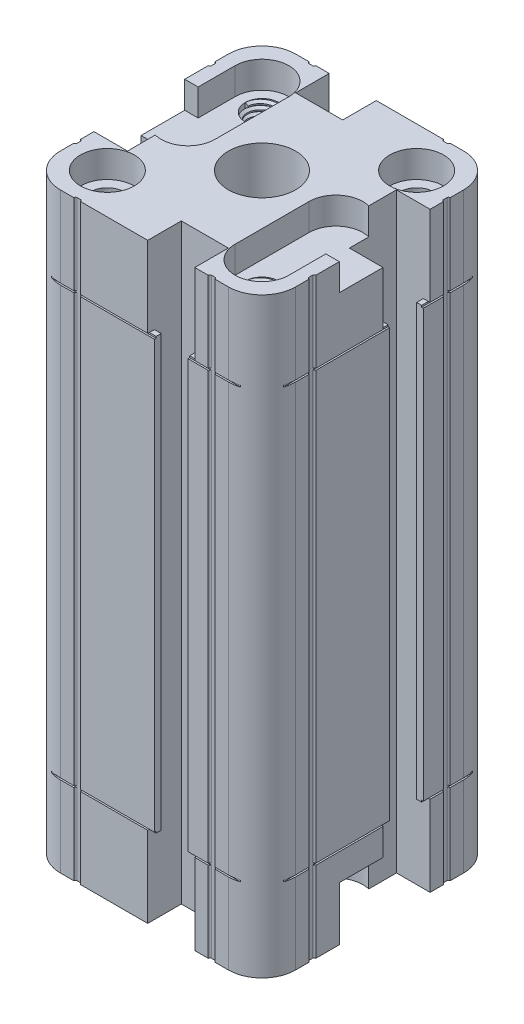
SolidWorks part; units mm, degrees
ref_plane "Front Plane" through (0, 0, 0) normal (0, 0, 1) x (1, 0, 0)
ref_plane "Top Plane" through (0, 0, 0) normal (0, 1, 0) x (1, 0, 0)
ref_plane "Right Plane" through (0, 0, 0) normal (1, 0, 0) x (0, 0, -1)
sketch "Sketch1" plane through (0, 0, 0) normal (0, 1, 0) x (1, 0, 0)
  line L1 (0, 0) -> (35, 0)
  line L2 (0, 0) -> (0, 35)
  line L3 (0, 35) -> (35, 35)
  line L4 (35, 0) -> (35, 35)
  dimension "D1" = 35
  dimension "D2" = 35
extrude "Boss-Extrude1" add sketch "Sketch1" along normal blind 88
sketch "Sketch2" plane through (0, 0, 0) normal (0, -1, 0) x (-1, 0, 0)
  line L0 (0, 0) -> (-35, 0) construction
  line L1 (0, 35) -> (0, 0) construction
  line L2 (-29, 6) -> (-29, 17) construction
  line L3 (-33, 6) -> (-33, 17)
  line L4 (-25, 6) -> (-25, 17)
  line L5 (-35, 0) -> (-35, 35) construction
  line L6 (-35, 35) -> (0, 35) construction
  line L7 (-6, 18) -> (-6, 29) construction
  line L8 (-10, 18) -> (-10, 29)
  line L9 (-2, 18) -> (-2, 29)
  circle A0 centre (-6, 6) radius 4
  circle A1 centre (-29, 29) radius 4
  arc A2 (-33, 6) -> (-25, 6) centre (-29, 6) ccw
  arc A3 (-25, 17) -> (-33, 17) centre (-29, 17) ccw
  arc A4 (-10, 18) -> (-2, 18) centre (-6, 18) ccw
  arc A5 (-2, 29) -> (-10, 29) centre (-6, 29) ccw
  point P10 (-29, 11.5)
  point P21 (-6, 23.5)
  dimension "D1" = 8
  dimension "D4" = 4
  dimension "D5" = 11
  dimension "D10" = 4
  dimension "D11" = 6
  dimension "D2" = 6
  dimension "D3" = 6
  dimension "D6" = 6
  dimension "D7" = 6
  dimension "D8" = 6
  dimension "D9" = 11
extrude "Cut-Extrude1" cut sketch "Sketch2" against normal blind 8
sketch "Sketch3" plane through (0, 0, 0) normal (0, -1, 0) x (-1, 0, 0)
  line L0 (0, 35) -> (0, 0) construction
  line L1 (-5, 23.5) -> (0, 23.5)
  line L2 (-5, 23.5) -> (-5, 14.127)
  line L3 (-5, 14.127) -> (0, 14.127)
  line L4 (0, 23.5) -> (0, 14.127)
  line L5 (-2, 18) -> (-2, 29) construction
  line L6 (-35, 20.873) -> (-30, 20.873)
  line L7 (-35, 20.873) -> (-35, 11.5)
  line L8 (-35, 11.5) -> (-30, 11.5)
  line L9 (-30, 20.873) -> (-30, 11.5)
  line L10 (-35, 0) -> (-35, 35) construction
  line L11 (-33, 17) -> (-33, 6) construction
  arc A2 (-25, 17) -> (-33, 17) centre (-29, 17) ccw construction
  arc A3 (-10, 18) -> (-2, 18) centre (-6, 18) ccw construction
  point P13 (-2, 23.5)
  point P25 (-32.5, 20.873)
  point P34 (-33, 11.5)
  dimension "D1" = 5
  dimension "D2" = 5
extrude "Cut-Extrude2" cut sketch "Sketch3" against normal up to surface (8 mm away) up to face at (6, 8, -23.5)
sketch "Sketch5" plane through (0, 0, 0) normal (0, -1, 0) x (1, 0, 0)
  line L0 (35, -20.873) -> (35, -35) construction
  line L1 (5, -17) -> (0, -17)
  line L2 (5, -17) -> (5, -10)
  line L3 (5, -10) -> (0, -10)
  line L4 (0, -17) -> (0, -10)
  line L5 (30, -18) -> (35, -18)
  line L6 (30, -18) -> (30, -25)
  line L7 (30, -25) -> (35, -25)
  line L8 (35, -18) -> (35, -25)
  line L9 (0, 0) -> (35, 0) construction
  line L10 (18, 0) -> (25, 0)
  line L11 (18, 0) -> (18, -5)
  line L12 (18, -5) -> (25, -5)
  line L13 (25, 0) -> (25, -5)
  line L14 (35, -35) -> (0, -35) construction
  line L15 (10, -35) -> (17, -35)
  line L16 (10, -35) -> (10, -30)
  line L17 (10, -30) -> (17, -30)
  line L18 (17, -35) -> (17, -30)
  circle A0 centre (6, -6) radius 4 construction
  circle A1 centre (29, -29) radius 4 construction
  dimension "D1" = 7
  dimension "D2" = 7
  dimension "D3" = 5
  dimension "D4" = 7
  dimension "D5" = 10
  dimension "D6" = 7
  dimension "D7" = 5
  dimension "D8" = 10
extrude "Cut-Extrude3" cut sketch "Sketch5" against normal blind 12
sketch "Sketch6" plane through (0, 12, 0) normal (0, -1, 0) x (1, 0, 0)
  line L6 (0, -16) -> (1, -16)
  line L7 (0, -10) -> (0, -17) construction
  line L8 (1, -16) -> (1, -17)
  line L9 (0, -17) -> (5, -17) construction
  line L10 (1, -17) -> (5, -17)
  line L11 (5, -17) -> (5, -10)
  line L12 (5, -10) -> (1, -10)
  line L13 (5, -10) -> (0, -10) construction
  line L14 (1, -10) -> (1, -11)
  line L15 (1, -11) -> (0, -11)
  line L16 (0, -11) -> (0, -16)
  line L17 (19, 0) -> (19, -1)
  line L18 (25, 0) -> (18, 0) construction
  line L19 (19, -1) -> (18, -1)
  line L20 (18, 0) -> (18, -5) construction
  line L21 (18, -1) -> (18, -5)
  line L22 (18, -5) -> (25, -5)
  line L23 (25, -5) -> (25, -1.01)
  line L24 (25, -5) -> (25, 0) construction
  line L25 (25, -1.01) -> (24, -1.01)
  line L26 (24, -1.01) -> (24, 0)
  line L27 (24, 0) -> (19, 0)
  line L28 (35, -19) -> (34, -19)
  line L29 (35, -25) -> (35, -18) construction
  line L30 (34, -19) -> (34, -18)
  line L31 (35, -18) -> (30, -18) construction
  line L32 (34, -18) -> (30, -18)
  line L33 (30, -18) -> (30, -25)
  line L34 (30, -25) -> (34, -25)
  line L35 (30, -25) -> (35, -25) construction
  line L36 (34, -25) -> (34, -24)
  line L37 (34, -24) -> (35, -24)
  line L38 (35, -24) -> (35, -19)
  line L39 (11, -35) -> (11, -34)
  line L40 (10, -35) -> (17, -35) construction
  line L41 (11, -34) -> (10, -34)
  line L42 (10, -30) -> (10, -35) construction
  line L43 (10, -34) -> (10, -30)
  line L44 (10, -30) -> (17, -30)
  line L45 (17, -30) -> (17, -34)
  line L46 (17, -35) -> (17, -30) construction
  line L47 (17, -34) -> (16, -34)
  line L48 (16, -34) -> (16, -35)
  line L49 (16, -35) -> (11, -35)
  dimension "D1" = 1
  dimension "D2" = 1
  dimension "D3" = 1
  dimension "D4" = 1
extrude "Cut-Extrude4" cut sketch "Sketch6" against normal blind 64
sketch "Sketch7" plane through (0, 88, 0) normal (0, 1, 0) x (1, 0, 0)
  line L0 (6, 29) -> (6, 18) construction
  line L1 (10, 29) -> (10, 18)
  line L2 (2, 29) -> (2, 18)
  line L3 (29, 17) -> (29, 6) construction
  line L4 (33, 17) -> (33, 6)
  line L5 (25, 17) -> (25, 6)
  arc A2 (10, 29) -> (2, 29) centre (6, 29) ccw
  arc A6 (2, 18) -> (10, 18) centre (6, 18) ccw
  circle A8 centre (29, 29) radius 4
  arc A9 (10, 29) -> (2, 29) centre (6, 29) ccw construction
  arc A10 (33, 17) -> (25, 17) centre (29, 17) ccw
  arc A11 (25, 6) -> (33, 6) centre (29, 6) ccw
  arc A12 (33, 17) -> (25, 17) centre (29, 17) ccw construction
  circle A13 centre (6, 6) radius 4
  point P4 (6, 23.5)
  point P14 (29, 11.5)
extrude "Cut-Extrude5" cut sketch "Sketch7" against normal blind 4
sketch "Sketch9" plane through (0, 88, 0) normal (0, 1, 0) x (1, 0, 0)
  line L1 (0, 23.5) -> (5, 23.5)
  line L2 (0, 23.5) -> (0, 14.127)
  line L3 (0, 14.127) -> (5, 14.127)
  line L4 (5, 23.5) -> (5, 14.127)
  line L5 (35, 20.873) -> (30, 20.873)
  line L6 (35, 20.873) -> (35, 11.5)
  line L7 (35, 11.5) -> (30, 11.5)
  line L8 (30, 20.873) -> (30, 11.5)
extrude "Cut-Extrude7" cut sketch "Sketch9" against normal up to surface (4 mm away) up to face at (6, 84, -23.5)
sketch "Sketch10" plane through (0, 88, 0) normal (0, 1, 0) x (1, 0, 0)
  line L1 (10, 30) -> (17, 30)
  line L2 (10, 30) -> (10, 35)
  line L3 (10, 35) -> (17, 35)
  line L4 (17, 30) -> (17, 35)
  line L5 (35, 25) -> (30, 25)
  line L6 (35, 25) -> (35, 18)
  line L7 (35, 18) -> (30, 18)
  line L8 (30, 25) -> (30, 18)
  line L9 (5, 10) -> (0, 10)
  line L10 (5, 10) -> (5, 17)
  line L11 (5, 17) -> (0, 17)
  line L12 (0, 10) -> (0, 17)
  line L13 (25, 5) -> (18, 5)
  line L14 (25, 5) -> (25, 0)
  line L15 (25, 0) -> (18, 0)
  line L16 (18, 5) -> (18, 0)
extrude "Cut-Extrude8" cut sketch "Sketch10" against normal up to surface (12 mm away) up to face at (1.75, 76, -13.5)
sketch "Sketch11" plane through (0, 88, 0) normal (0, 1, 0) x (1, 0, 0)
  line L0 (10, 35) -> (0, 35) construction
  line L1 (7, 35) -> (8, 35)
  line L2 (7, 35) -> (7, 34.75)
  line L3 (7, 34.75) -> (8, 34.75)
  line L4 (8, 35) -> (8, 34.75)
  line L5 (0, 35) -> (0, 23.5) construction
  line L6 (35, 35) -> (17, 35) construction
  line L7 (27, 35) -> (28, 35)
  line L8 (27, 35) -> (27, 34.75)
  line L9 (27, 34.75) -> (28, 34.75)
  line L10 (28, 35) -> (28, 34.75)
  line L11 (35, 25) -> (35, 35) construction
  line L12 (35, 0) -> (35, 11.5) construction
  line L13 (35, 28) -> (34.75, 28)
  line L14 (35, 28) -> (35, 27)
  line L15 (35, 27) -> (34.75, 27)
  line L16 (34.75, 28) -> (34.75, 27)
  line L17 (35, 8) -> (34.75, 8)
  line L18 (35, 8) -> (35, 7)
  line L19 (35, 7) -> (34.75, 7)
  line L20 (34.75, 8) -> (34.75, 7)
  line L21 (25, 0) -> (35, 0) construction
  line L22 (27, 0) -> (28, 0)
  line L23 (27, 0) -> (27, 0.25)
  line L24 (27, 0.25) -> (28, 0.25)
  line L25 (28, 0) -> (28, 0.25)
  line L26 (0, 0) -> (18, 0) construction
  line L27 (8, 0) -> (7, 0)
  line L28 (8, 0) -> (8, 0.25)
  line L29 (8, 0.25) -> (7, 0.25)
  line L30 (7, 0) -> (7, 0.25)
  line L31 (0, 10) -> (0, 0) construction
  line L32 (0, 8) -> (0.25, 8)
  line L33 (0, 8) -> (0, 7)
  line L34 (0, 7) -> (0.25, 7)
  line L35 (0.25, 8) -> (0.25, 7)
  line L36 (10, 35) -> (0, 35) construction
  line L37 (0, 28) -> (0.25, 28)
  line L38 (0, 28) -> (0, 27)
  line L39 (0, 27) -> (0.25, 27)
  line L40 (0.25, 28) -> (0.25, 27)
  dimension "D1" = 7
  dimension "D2" = 1
  dimension "D3" = 0.25
  dimension "D4" = 7
  dimension "D5" = 7
  dimension "D6" = 7
  dimension "D7" = 7
  dimension "D8" = 7
  dimension "D9" = 7
  dimension "D10" = 7
extrude "Cut-Extrude9" cut sketch "Sketch11" against normal through all
fillet "Fillet2" radius 0.25 16 edges at (0.25, 44, -7) (0.25, 44, -8) (7, 44, -0.25) (8, 44, -0.25) (28, 44, -0.25) (27, 44, -0.25) (34.75, 44, -8) (34.75, 44, -7) (34.75, 44, -27) (34.75, 44, -28) (27, 44, -34.75) (28, 44, -34.75) (7, 44, -34.75) (8, 44, -34.75) (0.25, 44, -27) (0.25, 44, -28)
sketch "Sketch12" plane through (0, 0, 0) normal (-1, 0, 0) x (0, 0, 1)
  line L0 (-35, 88) -> (-35, 0) construction
  line L1 (-35, 12.25) -> (-34.75, 12.25)
  line L2 (-35, 12.25) -> (-35, 12)
  line L3 (-35, 12) -> (-34.75, 12)
  line L4 (-34.75, 12.25) -> (-34.75, 12)
  line L5 (0, 88) -> (0, 0) construction
  line L6 (0, 12.25) -> (-0.25, 12.25)
  line L7 (0, 12.25) -> (0, 12)
  line L8 (0, 12) -> (-0.25, 12)
  line L9 (-0.25, 12.25) -> (-0.25, 12)
  line L10 (-35, 0) -> (-28, 0) construction
  line L11 (-7, 0) -> (0, 0) construction
  line L12 (-35, 88) -> (-28, 88) construction
  line L13 (-35, 76) -> (-34.75, 76)
  line L14 (-35, 76) -> (-35, 75.75)
  line L15 (-35, 75.75) -> (-34.75, 75.75)
  line L16 (-34.75, 76) -> (-34.75, 75.75)
  line L17 (0, 76) -> (-0.25, 76)
  line L18 (0, 76) -> (0, 75.75)
  line L19 (0, 75.75) -> (-0.25, 75.75)
  line L20 (-0.25, 76) -> (-0.25, 75.75)
  line L21 (-7, 88) -> (0, 88) construction
  dimension "D1" = 0.25
  dimension "D2" = 0.25
  dimension "D3" = 0.25
  dimension "D4" = 0.25
  dimension "D5" = 12
  dimension "D6" = 12
  dimension "D7" = 0.25
  dimension "D8" = 0.25
  dimension "D9" = 0.25
  dimension "D10" = 0.25
  dimension "D11" = 12
  dimension "D12" = 12
fillet "Fillet4" radius 5 4 edges at (35, 44, 0) (0, 44, 0) (35, 44, -35) (0, 44, -35)
extrude "Cut-Extrude12" cut sketch "Sketch12" against normal through all
sketch "Sketch14" plane through (0, 0, 0) normal (0, 0, 1) x (1, 0, 0)
  line L0 (35, 88) -> (35, 0) construction
  line L9 (0, 12.25) -> (0, 12) construction
  line L10 (0, 12.25) -> (0.25, 12.25)
  line L11 (0, 12.25) -> (0, 12)
  line L12 (0, 12) -> (0.25, 12)
  line L13 (0.25, 12.25) -> (0.25, 12)
  line L14 (0, 12.25) -> (0, 12) construction
  line L16 (35, 12.25) -> (34.75, 12.25)
  line L17 (35, 12.25) -> (35, 12)
  line L18 (35, 12) -> (34.75, 12)
  line L19 (34.75, 12.25) -> (34.75, 12)
  line L24 (0, 0) -> (0, 88) construction
  line L25 (0, 76) -> (0.25, 76)
  line L26 (0, 76) -> (0, 75.75)
  line L27 (0, 75.75) -> (0.25, 75.75)
  line L28 (0.25, 76) -> (0.25, 75.75)
  line L29 (5, 88) -> (0, 88) construction
  line L31 (35, 76) -> (34.75, 76)
  line L32 (35, 76) -> (35, 75.75)
  line L33 (35, 75.75) -> (34.75, 75.75)
  line L34 (34.75, 76) -> (34.75, 75.75)
  dimension "D1" = 0.25
  dimension "D2" = 0.25
  dimension "D3" = 0.25
  dimension "D5" = 0.25
  dimension "D6" = 0.25
  dimension "D7" = 0.25
  dimension "D8" = 0.25
  dimension "D9" = 12
extrude "Cut-Extrude13" cut sketch "Sketch14" against normal through all
sketch "Sketch15" plane through (0, 8, 0) normal (0, -1, 0) x (-1, 0, 0)
  circle A0 centre (-6, 6) radius 2.5
  circle A1 centre (-29, 29) radius 2.5
  circle A3 centre (-29, 6) radius 2.5
  circle A4 centre (-6, 29) radius 2.5
  dimension "D1" = 5
extrude "Cut-Extrude14" cut sketch "Sketch15" against normal up to vertex (4 mm away) up to point (0.25, 12, -3.4388)
thread "Thread2" pitch 0.8 method extrude profile "Thread Profile2" start angle 0, offset 0, length 0, pitch 0.8, diameter 5
ref_plane "Plane2" through (31.5, 8, -6) normal (0, 0, 1) x (1, 0, 0)
sketch "Thread Profile2" plane through (31.5, 8, -6) normal (0, 0, 1) x (1, 0, 0)
  line L0 (0, 0) -> (0, 0.8) construction
  line L11 (0, 0) -> (0, 0.7)
  line L12 (0, 0.7) -> (-0.433, 0.45)
  line L13 (-0.433, 0.45) -> (-0.433, 0.25)
  line L15 (-0.433, 0.25) -> (0, 0)
  line L17 (-0.433, 0.35) -> (0, 0.35) construction
  point P2 (0, 0)
  dimension "Pitch" = 0.8
  dimension "Profile_Angle" = 60
  dimension "Profile_Land" = 0.2
  dimension "Profile_Height" = 0.433
thread "Thread3" pitch 0.8 method extrude profile "Thread Profile3" start angle 0, offset 0, length 0, pitch 0.8, diameter 5
ref_plane "Plane3" through (8.5, 8, -29) normal (0, 0, 1) x (1, 0, 0)
sketch "Thread Profile3" plane through (8.5, 8, -29) normal (0, 0, 1) x (1, 0, 0)
  line L0 (0, 0) -> (0, 0.8) construction
  line L11 (0, 0) -> (0, 0.7)
  line L12 (0, 0.7) -> (-0.433, 0.45)
  line L13 (-0.433, 0.45) -> (-0.433, 0.25)
  line L15 (-0.433, 0.25) -> (0, 0)
  line L17 (-0.433, 0.35) -> (0, 0.35) construction
  point P2 (0, 0)
  dimension "Pitch" = 0.8
  dimension "Profile_Angle" = 60
  dimension "Profile_Land" = 0.2
  dimension "Profile_Height" = 0.433
sketch "Sketch24" plane through (0, 84, 0) normal (0, 1, 0) x (1, 0, 0)
  circle A0 centre (6, 29) radius 2.5
  circle A1 centre (29, 29) radius 2.5
  circle A2 centre (6, 6) radius 2.5
  circle A3 centre (29, 6) radius 2.5
  dimension "D1" = 5
extrude "Cut-Extrude15" cut sketch "Sketch24" against normal up to vertex (8 mm away) up to point (35, 76, -5)
thread "Thread5" pitch 0.8 method extrude profile "Thread Profile5" start angle 0, offset 0, length 0, pitch 0.8, diameter 5
ref_plane "Plane5" through (26.5, 84, -6) normal (0, 0, 1) x (-1, 0, 0)
sketch "Thread Profile5" plane through (26.5, 84, -6) normal (0, 0, 1) x (-1, 0, 0)
  line L0 (0, 0) -> (0, 0.8) construction
  line L11 (0, 0) -> (0, 0.7)
  line L12 (0, 0.7) -> (-0.433, 0.45)
  line L13 (-0.433, 0.45) -> (-0.433, 0.25)
  line L15 (-0.433, 0.25) -> (0, 0)
  line L17 (-0.433, 0.35) -> (0, 0.35) construction
  point P2 (0, 0)
  dimension "Pitch" = 0.8
  dimension "Profile_Angle" = 60
  dimension "Profile_Land" = 0.2
  dimension "Profile_Height" = 0.433
thread "Thread8" pitch 0.8 method extrude profile "Thread Profile8" start angle 0, offset 0, length 0, pitch 0.8, diameter 5
ref_plane "Plane8" through (3.5, 84, -29) normal (0, 0, 1) x (-1, 0, 0)
sketch "Thread Profile8" plane through (3.5, 84, -29) normal (0, 0, 1) x (-1, 0, 0)
  line L0 (0, 0) -> (0, 0.8) construction
  line L11 (0, 0) -> (0, 0.7)
  line L12 (0, 0.7) -> (-0.433, 0.45)
  line L13 (-0.433, 0.45) -> (-0.433, 0.25)
  line L15 (-0.433, 0.25) -> (0, 0)
  line L17 (-0.433, 0.35) -> (0, 0.35) construction
  point P2 (0, 0)
  dimension "Pitch" = 0.8
  dimension "Profile_Angle" = 60
  dimension "Profile_Land" = 0.2
  dimension "Profile_Height" = 0.433
sketch "Sketch33" plane through (0, 0, 0) normal (0, -1, 0) x (-1, 0, 0)
  line L0 (-27, 35) -> (-17, 35) construction
  line L1 (0, 23.5) -> (0, 17) construction
  circle A0 centre (-17.5, 17.5) radius 6
  dimension "D1" = 12
  dimension "D2" = 17.5
  dimension "D3" = 17.5
extrude "Cut-Extrude16" cut sketch "Sketch33" against normal blind 3
sketch "Sketch35" plane through (0, 88, 0) normal (0, 1, 0) x (1, 0, 0)
  line L0 (27, 35) -> (17, 35) construction
  line L1 (0, 17) -> (0, 23.5) construction
  circle A0 centre (17.5, 17.5) radius 5
  dimension "D1" = 10
  dimension "D2" = 17.5
  dimension "D3" = 17.5
extrude "Cut-Extrude19" cut sketch "Sketch15<3>" against normal through all contours A1 | A0
sketch "Sketch15<3>" plane through (0, 8, 0) normal (0, -1, 0) x (-1, 0, 0) same geometry as "Sketch15"
ref_plane "Plane9" through (0, 75.75, 0) normal (0, -1, 0) x (-1, 0, 0)
sketch "Sketch36" plane through (0, 75.75, 0) normal (0, -1, 0) x (-1, 0, 0)
  line L0 (-35, 28) -> (-35, 30) construction
  line L1 (-27.5, 27.5) -> (-7.5, 27.5)
  line L2 (-27.5, 27.5) -> (-27.5, 7.5)
  line L3 (-27.5, 7.5) -> (-7.5, 7.5)
  line L4 (-7.5, 27.5) -> (-7.5, 7.5)
  line L5 (-10, 35) -> (-8, 35) construction
  line L6 (-8, 0) -> (-18, 0) construction
  line L7 (0, 23.5) -> (0, 17) construction
  dimension "D1" = 7.5
  dimension "D2" = 7.5
  dimension "D3" = 7.5
  dimension "D4" = 7.5
extrude "Cut-Extrude20" cut sketch "Sketch36" along normal blind 52
extrude "Cut-Extrude21" cut sketch "Sketch35" against normal up to next
